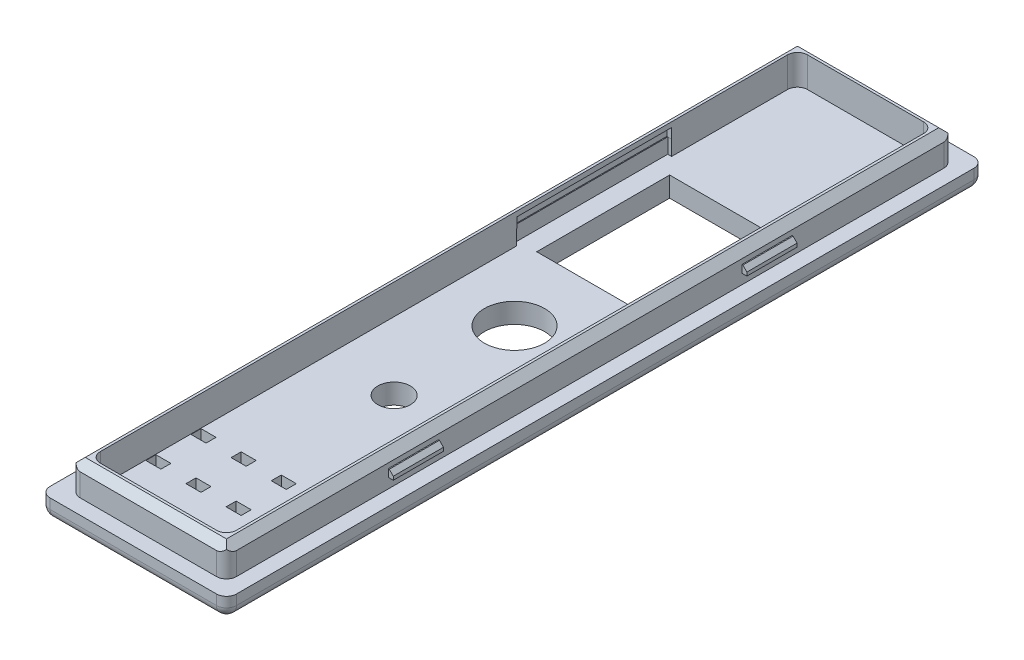
SolidWorks part; units mm, degrees
ref_plane "Plan de face" through (0, 0, 0) normal (0, 0, 1) x (1, 0, 0)
ref_plane "Plan de dessus" through (0, 0, 0) normal (0, 1, 0) x (1, 0, 0)
ref_plane "Plan de droite" through (0, 0, 0) normal (1, 0, 0) x (0, 0, -1)
sketch "Sketch1" plane through (0, 0, 0) normal (0, 1, 0) x (1, 0, 0)
  line L1 (-18.58, -75.5) -> (18.58, -75.5)
  line L2 (-18.58, -75.5) -> (-18.58, 75.5)
  line L3 (-18.58, 75.5) -> (18.58, 75.5)
  line L4 (18.58, -75.5) -> (18.58, 75.5)
  line L5 (-18.58, -75.5) -> (18.58, 75.5) construction
  line L6 (-18.58, 75.5) -> (18.58, -75.5) construction
  point P0 (0, 0)
  dimension "D1" = 37.16
  dimension "D2" = 151
extrude "Boss-Extrude1" add sketch "Sketch1" along normal blind 4
sketch "Sketch3" plane through (0, 4, 0) normal (0, 1, 0) x (1, 0, 0)
  line L1 (18.58, -75.5) -> (-18.58, -75.5)
  line L2 (18.58, -75.5) -> (18.58, 75.5)
  line L3 (18.58, 75.5) -> (-18.58, 75.5)
  line L4 (-18.58, -75.5) -> (-18.58, 75.5)
  line L5 (18.58, -75.5) -> (-18.58, 75.5) construction
  line L6 (18.58, 75.5) -> (-18.58, -75.5) construction
  line L7 (15.58, -72.5) -> (-15.58, -72.5)
  line L8 (15.58, -72.5) -> (15.58, 72.5)
  line L9 (15.58, 72.5) -> (-15.58, 72.5)
  line L10 (-15.58, -72.5) -> (-15.58, 72.5)
  line L11 (15.58, -72.5) -> (-15.58, 72.5) construction
  line L12 (15.58, 72.5) -> (-15.58, -72.5) construction
  line L13 (13.58, -70.5) -> (-13.58, -70.5)
  line L14 (13.58, -70.5) -> (13.58, 70.5)
  line L15 (13.58, 70.5) -> (-13.58, 70.5)
  line L16 (-13.58, -70.5) -> (-13.58, 70.5)
  line L17 (13.58, -70.5) -> (-13.58, 70.5) construction
  line L18 (13.58, 70.5) -> (-13.58, -70.5) construction
  point P0 (0, 0)
  point P7 (0, 0)
  point P12 (0, 0)
  dimension "D1" = 151
  dimension "D2" = 37.16
  dimension "D3" = 145
  dimension "D4" = 31.16
  dimension "D5" = 27.16
  dimension "D6" = 141
extrude "Boss-Extrude2" add sketch "Sketch3" along normal blind 4 contours L10 L7 L8 L9 L13 L16 L15 L14 region at (0, 4, 71.0169)
sketch "Sketch12" plane through (0, 8, 0) normal (0, 1, 0) x (1, 0, 0)
  line L1 (13.58, -70.5) -> (-13.58, -70.5)
  line L2 (13.58, -70.5) -> (13.58, 70.5)
  line L3 (13.58, 70.5) -> (-13.58, 70.5)
  line L4 (-13.58, -70.5) -> (-13.58, 70.5)
  line L5 (13.58, -70.5) -> (-13.58, 70.5) construction
  line L6 (13.58, 70.5) -> (-13.58, -70.5) construction
  line L7 (14.08, -71) -> (-14.08, -71)
  line L8 (14.08, -71) -> (14.08, 71)
  line L9 (14.08, 71) -> (-14.08, 71)
  line L10 (-14.08, -71) -> (-14.08, 71)
  line L11 (14.08, -71) -> (-14.08, 71) construction
  line L12 (14.08, 71) -> (-14.08, -71) construction
  point P0 (0, 0)
  point P7 (0, 0)
  dimension "D1" = 27.16
  dimension "D2" = 141
  dimension "D3" = 28.16
  dimension "D4" = 142
extrude "Boss-Extrude4" add sketch "Sketch12" along normal blind 2
chamfer "Chamfer1" distance 2 angle 45 4 edges at (14.08, 8, 0) (0, 8, 71) (0, 8, -71) (-14.08, 8, 0)
fillet "Fillet1" radius 2 16 edges at (-13.58, 7, 70.5) (13.58, 7, 70.5) (13.58, 7, -70.5) (-13.58, 7, -70.5) (-15.58, 6.25, -72.5) (-18.58, 2, -75.5) (18.58, 2, -75.5) (15.58, 6.25, -72.5) (15.58, 6.25, 72.5) (18.58, 2, 75.5) (-15.58, 6.25, 72.5) (-18.58, 2, 75.5) (0, 0, -75.5) (-18.58, 0, 0) (0, 0, 75.5) (18.58, 0, 0)
sketch "Sketch5" plane through (0, 7, 0) normal (0, 1, 0) x (1, 0, 0)
  line L0 (-16.53, -71.5) -> (-16.53, 71.5) construction
  line L1 (-16.53, 14.5) -> (16.53, 14.5)
  line L2 (-16.53, 14.5) -> (-16.53, 45.4023)
  line L3 (-16.53, 45.4023) -> (16.53, 45.4023)
  line L4 (16.53, 14.5) -> (16.53, 45.4023)
  line L5 (16.53, -71.5) -> (16.53, 71.5) construction
  line L7 (-16.53, 45.4023) -> (-13.58, 45.4023)
  line L8 (-13.58, -68.5) -> (-13.58, 68.5) construction
  line L9 (-13.58, 45.4023) -> (-16.53, 45.4023) construction
  line L10 (-14.3506, 45.4023) -> (-14.3506, 14.5)
  line L11 (16.53, 45.4023) -> (14.53, 45.4023) construction
  line L12 (14.53, -69.5) -> (14.53, 69.5) construction
  line L14 (14.4112, 45.4023) -> (14.4112, 14.5)
  line L15 (13.58, -72.5) -> (-13.58, -72.5) construction
  dimension "D1" = 87
extrude "Cut-Extrude1" cut sketch "Sketch5" against normal blind 3 contours L14 L3 L7 L10 L1 region at (0.0303, 7, -29.9511)
sketch "Sketch6" plane through (0, 0, 0) normal (0, -1, 0) x (1, 0, 0)
  line L0 (-10.5764, -15.5) -> (9.4236, -42) construction
  line L1 (-10.5764, -42) -> (9.4236, -42)
  line L2 (-10.5764, -42) -> (-10.5764, -15.5)
  line L3 (-10.5764, -15.5) -> (9.4236, -15.5)
  line L4 (9.4236, -42) -> (9.4236, -15.5)
  line L5 (-16.58, 73.5) -> (-16.58, -73.5) construction
  line L7 (16.58, 73.5) -> (-16.58, 73.5) construction
  line L8 (9.6736, -42.25) -> (-10.8264, -42.25)
  line L9 (9.6736, -42.25) -> (9.6736, -15.25)
  line L10 (9.6736, -15.25) -> (-10.8264, -15.25)
  line L11 (-10.8264, -42.25) -> (-10.8264, -15.25)
  line L12 (9.6736, -42.25) -> (-10.8264, -15.25) construction
  line L13 (9.6736, -15.25) -> (-10.8264, -42.25) construction
  point P8 (-0.5764, -28.75)
  dimension "D1" = 6.0036
  dimension "D3" = 20
  dimension "D4" = 26.5
  dimension "D5" = 20.5
  dimension "D6" = 27
  dimension "D2" = 89
extrude "Cut-Extrude2" cut sketch "Sketch6" against normal blind 12 contours L2 L1 L4 L3
sketch "Sketch13" plane through (0, 7, 0) normal (0, -1, 0) x (1, 0, 0)
  line L5 (-14.5267, -14.5677) -> (14.7477, -14.5677)
  line L6 (-14.5267, -14.5677) -> (-14.5267, -45.3928)
  line L7 (-14.5267, -45.3928) -> (14.7477, -45.3928)
  line L8 (14.7477, -14.5677) -> (14.7477, -45.3928)
extrude "Cut-Extrude7" cut sketch "Sketch13" against normal blind 2
sketch "Sketch7" plane through (0, 0, -15.5) normal (0, 0, -1) x (-1, 0, 0)
  line L1 (-9.4236, 0) -> (-5.2619, 0)
  line L2 (-9.4236, 0) -> (-9.4236, 0.5293)
  line L3 (-9.4236, 0.5293) -> (-5.2619, 0.5293)
  line L4 (-5.2619, 0) -> (-5.2619, 0.5293)
extrude "Boss-Extrude3" add sketch "Sketch7" along normal blind 29
sketch "Sketch8" plane through (0, 0, 0) normal (0, -1, 0) x (1, 0, 0)
  line L0 (0, 0) -> (0, -60.7193) construction
  line L2 (-10.5764, -15.5) -> (5.2619, -15.5) construction
  circle A0 centre (0, -0.5) radius 6
  dimension "D1" = 12
  dimension "D2" = 15
extrude "Cut-Extrude3" cut sketch "Sketch8" against normal blind 29
sketch "Sketch9" plane through (0, 0, 0) normal (0, -1, 0) x (1, 0, 0)
  line L0 (0, 0) -> (0, 73.5) construction
  line L1 (16.58, 73.5) -> (-16.58, 73.5) construction
  circle A0 centre (0, 23.5) radius 3.25
  dimension "D1" = 6.5
  dimension "D2" = 50
extrude "Cut-Extrude4" cut sketch "Sketch9" against normal blind 5
sketch "Sketch10" plane through (-14.8069, 0, -2.7101) normal (0, -1, 0) x (0, 0, 1)
  text T0 "Thermomètre 4G" font "Arial" height 5
extrude "Cut-Extrude5" cut sketch "Sketch10" against normal blind 0.5
sketch "Sketch11" plane through (49.3642, 0, 60.559) normal (0, -1, 0) x (0, 0, 1)
  line L0 (-43.0674, 47.2582) -> (-31.0674, 47.2582) construction
  line L1 (-46.7993, 47.2582) -> (-43.0674, 47.2582) construction
  line L2 (-37.0674, 49.3707) -> (-37.0674, 44.3746) construction
  circle A0 centre (-37.0674, 49.3707) radius 3.2394 construction
  text T0 "1" font "Arial" height 5
  text T1 "0" font "Arial" height 5
  point P0 (-37.0674, 47.2582)
  point P8 (-37.0674, 49.3707)
  dimension "D1" = 12
  dimension "D2" = 3.7319
extrude "Cut-Extrude6" cut sketch "Sketch11" against normal blind 0.5
sketch "Esquisse1" plane through (0, 0, 0) normal (0, -1, 0) x (-1, 0, 0)
  line L0 (-5.5, -48.5) -> (-5.5, -50.5)
  line L5 (-13.5, -48.5) -> (-10.5, -48.5)
  line L6 (-13.5, -48.5) -> (-13.5, -50.5)
  line L7 (-13.5, -50.5) -> (-10.5, -50.5)
  line L8 (-10.5, -48.5) -> (-10.5, -50.5)
  line L9 (-5.5, -48.5) -> (-2.5, -48.5)
  line L10 (-2.5, -48.5) -> (-2.5, -50.5)
  line L11 (-5.5, -50.5) -> (-2.5, -50.5)
  line L12 (2.5, -48.5) -> (2.5, -50.5)
  line L13 (2.5, -48.5) -> (5.5, -48.5)
  line L14 (5.5, -48.5) -> (5.5, -50.5)
  line L15 (2.5, -50.5) -> (5.5, -50.5)
  line L16 (10.5, -48.5) -> (10.5, -50.5)
  line L17 (10.5, -48.5) -> (13.5, -48.5)
  line L18 (13.5, -48.5) -> (13.5, -50.5)
  line L19 (10.5, -50.5) -> (13.5, -50.5)
  line L20 (-5.5, -57.5) -> (-5.5, -59.5)
  line L21 (-5.5, -57.5) -> (-2.5, -57.5)
  line L22 (-2.5, -57.5) -> (-2.5, -59.5)
  line L23 (-5.5, -59.5) -> (-2.5, -59.5)
  line L24 (2.5, -57.5) -> (2.5, -59.5)
  line L25 (2.5, -57.5) -> (5.5, -57.5)
  line L26 (5.5, -57.5) -> (5.5, -59.5)
  line L27 (2.5, -59.5) -> (5.5, -59.5)
  line L28 (10.5, -57.5) -> (10.5, -59.5)
  line L29 (10.5, -57.5) -> (13.5, -57.5)
  line L30 (13.5, -57.5) -> (13.5, -59.5)
  line L31 (10.5, -59.5) -> (13.5, -59.5)
  line L32 (-5.5, -66.5) -> (-5.5, -68.5)
  line L33 (-5.5, -66.5) -> (-2.5, -66.5)
  line L34 (-2.5, -66.5) -> (-2.5, -68.5)
  line L35 (-5.5, -68.5) -> (-2.5, -68.5)
  line L36 (2.5, -66.5) -> (2.5, -68.5)
  line L37 (2.5, -66.5) -> (5.5, -66.5)
  line L38 (5.5, -66.5) -> (5.5, -68.5)
  line L39 (2.5, -68.5) -> (5.5, -68.5)
  line L40 (10.5, -66.5) -> (10.5, -68.5)
  line L41 (10.5, -66.5) -> (13.5, -66.5)
  line L42 (13.5, -66.5) -> (13.5, -68.5)
  line L43 (10.5, -68.5) -> (13.5, -68.5)
  line L176 (-13.5, -57.5) -> (-13.5, -59.5)
  line L177 (-13.5, -57.5) -> (-10.5, -57.5)
  line L178 (-10.5, -57.5) -> (-10.5, -59.5)
  line L179 (-13.5, -59.5) -> (-10.5, -59.5)
  line L180 (-13.5, -66.5) -> (-13.5, -68.5)
  line L181 (-13.5, -66.5) -> (-10.5, -66.5)
  line L182 (-10.5, -66.5) -> (-10.5, -68.5)
  line L183 (-13.5, -68.5) -> (-10.5, -68.5)
  line L185 (-13.5, -48.5) -> (13.5, -48.5) construction
  line L186 (-13.5, -48.5) -> (-13.5, -68.5) construction
  line L187 (-13.5, -68.5) -> (13.5, -68.5) construction
  line L188 (13.5, -48.5) -> (13.5, -68.5) construction
  line L189 (-16.58, -73.5) -> (16.58, -73.5) construction
  line L192 (-16.58, 73.5) -> (-16.58, -73.5) construction
  dimension "D2" = 2
  dimension "D3" = 33.16
  dimension "D7" = 3.08
  dimension "D8" = 5
  dimension "D5" = 4
extrude "Enlèv. mat.-Extru.1" cut sketch "Esquisse1" against normal blind 10
sketch "Esquisse2" plane through (-15.58, 0, 0) normal (-1, 0, 0) x (0, 0, 1)
  line L0 (0, 8.5) -> (-70.5, 8.5) construction
  line L2 (70.5, 8.5) -> (-70.5, 8.5) construction
  line L3 (73.5, 0) -> (-73.5, 0) construction
  line L5 (0, 8.5) -> (0, 0) construction
  line L6 (-40.25, 6) -> (-30.25, 6)
  line L7 (-40.25, 6) -> (-40.25, 7.5)
  line L8 (-40.25, 7.5) -> (-30.25, 7.5)
  line L9 (-30.25, 6) -> (-30.25, 7.5)
  line L12 (40.25, 7.5) -> (30.25, 7.5)
  line L13 (30.25, 6) -> (30.25, 7.5)
  line L14 (40.25, 6) -> (30.25, 6)
  line L15 (40.25, 6) -> (40.25, 7.5)
  point P8 (-62.7424, 16.3026)
  point P21 (0, 0)
  point P22 (0, 0)
  dimension "D1" = 1.5
  dimension "D2" = 10
  dimension "D4" = 6
extrude "Boss.-Extru.1" add sketch "Esquisse2" along normal blind 1 contours L14 L15 L12 L13 | L8 L7 L6 | L6 L9 L8 region at (-15.58, 6.75, -35.25) region at (-15.58, 6.75, 35.25)
sketch "Esquisse4" plane through (15.58, 0, 0) normal (1, 0, 0) x (0, 0, -1)
  line L0 (0, 8.5) -> (-70.5, 8.5) construction
  line L1 (73.5, 0) -> (-73.5, 0) construction
  line L3 (-35.25, 8.5) -> (-35.25, 5) construction
  line L5 (0, 8.5) -> (0, 0) construction
  line L6 (-40.25, 6) -> (-30.25, 6)
  line L7 (-40.25, 6) -> (-40.25, 7.5)
  line L8 (-40.25, 7.5) -> (-30.25, 7.5)
  line L9 (-30.25, 6) -> (-30.25, 7.5)
  line L10 (-40.25, 6) -> (-30.25, 7.5) construction
  line L11 (-40.25, 7.5) -> (-30.25, 6) construction
  line L12 (40.25, 7.5) -> (30.25, 7.5)
  line L13 (30.25, 6) -> (30.25, 7.5)
  line L14 (40.25, 6) -> (30.25, 6)
  line L15 (40.25, 6) -> (40.25, 7.5)
  point P10 (-35.25, 6.75)
  dimension "D1" = 1.5
  dimension "D2" = 10
  dimension "D3" = 6
extrude "Boss.-Extru.2" add sketch "Esquisse4" along normal blind 1
chamfer "Chanfrein1" distance 0.8 angle 45 4 edges at (-16.58, 7.5, 35.25) (-16.58, 7.5, -35.25) (16.58, 7.5, 35.25) (16.58, 7.5, -35.25)
equation "\"D1@Sketch1\"=31.16mm + 3*2"
equation "\"D4@Sketch3\"=\"D2@Sketch3\" - 2*3"
equation "\"D5@Sketch3\"=\"D4@Sketch3\"-2*2"
equation "\"D3@Sketch3\"=\"D1@Sketch3\"-3*2"
equation "\"D6@Sketch3\"=\"D3@Sketch3\"-2*2"
equation "\"D5@Sketch6\"=\"D3@Sketch6\"+0.5"
equation "\"D6@Sketch6\"=\"D4@Sketch6\"+0.5"
equation "\"D3@Sketch12\"=\"D1@Sketch12\"+1"
equation "\"D4@Sketch12\"=\"D2@Sketch12\"+1"
equation "\"D7@Esquisse1\"=(\"D3@Esquisse1\"-\"D4@Esquisse1\")/2"
